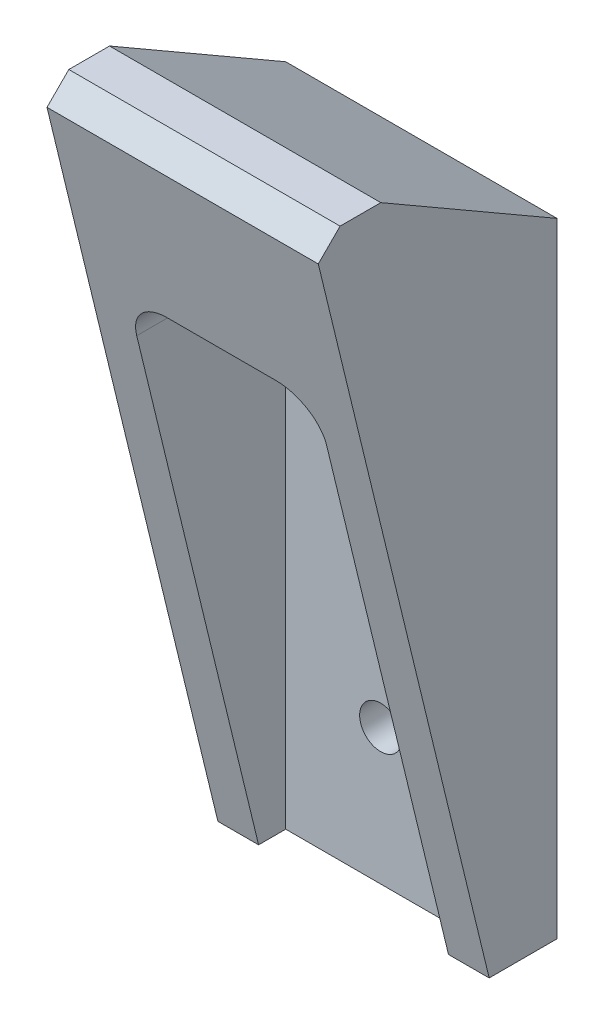
SolidWorks part; units mm, degrees
ref_plane "Front Plane" through (0, 0, 0) normal (0, 0, 1) x (1, 0, 0)
ref_plane "Top Plane" through (0, 0, 0) normal (0, 1, 0) x (1, 0, 0)
ref_plane "Right Plane" through (0, 0, 0) normal (1, 0, 0) x (0, 0, -1)
sketch "Sketch1" plane through (0, 0, 0) normal (1, 0, 0) x (0, 0, -1)
  line L0 (0, 0) -> (-5, 0)
  line L1 (0, 0) -> (0, 46)
  line L2 (0, 46) -> (-12.9904, 53.5)
  line L3 (-12.9904, 53.5) -> (-17.9904, 53.5)
  line L4 (-17.9904, 53.5) -> (-5, 0)
  dimension "D1" = 5
  dimension "D2" = 46
  dimension "D3" = 120
  dimension "D4" = 15
  dimension "D5" = 5
extrude "Boss-Extrude1" add sketch "Sketch1" along normal blind 20
ref_plane "Plane1" through (0, 0, 0) normal (0, -1, 0) x (-1, 0, 0)
ref_point "Point1"
ref_plane "Plane2" through (0, 0, 17.9904) normal (0, 0, 1) x (1, 0, 0)
sketch "Sketch4" plane through (0, 0, 17.9904) normal (0, 0, 1) x (1, 0, 0)
  line L0 (10, 0) -> (10, 53.5) construction
  line L1 (0, 0) -> (3, 0)
  line L2 (20, 0) -> (17, 0)
  line L3 (3, 0) -> (3, 40)
  line L4 (0, 53.5) -> (0, 0)
  line L5 (0, 0) -> (20, 0)
  line L6 (20, 0) -> (20, 53.5)
  line L7 (20, 53.5) -> (0, 53.5)
  line L8 (0, 53.5) -> (0, 0)
  line L9 (0, 0) -> (20, 0)
  line L10 (20, 0) -> (20, 53.5)
  line L11 (20, 53.5) -> (0, 53.5)
  line L12 (3, 40) -> (17, 40)
  line L13 (17, 40) -> (17, 0)
  dimension "D2" = 3
  dimension "D3" = 3
  dimension "D4" = 40
  dimension "D1" = 0
extrude "Cut-Extrude1" cut sketch "Sketch4" against normal offset from surface (14.9904 mm away) 3 contours L0 L9 L13 L12 | L9 L0 L12 L3 region at (6.5, 20, 17.9904) region at (13.5, 20, 17.9904) up to face at (10, 23, 0)
sketch "Sketch5" plane through (0, 0, 3) normal (0, 0, 1) x (1, 0, 0)
  line L0 (10, 0) -> (10, 53.1114) construction
  line L1 (17, 0) -> (3, 0) construction
  line L2 (17, 40) -> (3, 40) construction
  point P4 (10, 10)
  point P5 (10, 30)
  dimension "D1" = 10
  dimension "D2" = 10
fillet "Fillet1" radius 3 2 edges at (3, 40, 8.8562) (17, 40, 8.8562)
chamfer "Chamfer1" distance 2 angle 45 1 edges at (10, 53.5, 17.9904) first distance on face at (10, 53.5, 15.4904)
hole_wizard "M3 Clearance" positions "3DSketch1" profile "Sketch7" hole size "M" standard "ANSI Inch" end condition through all
sketch3d "3DSketch1"
  point P0 (10, 30, 3)
  point P3 (10, 10, 3)
sketch "Sketch7" plane through (10, 30, 3) normal (1, 0, 0) x (0, -1, 0)
  line L0 (0, 0) -> (0, 3)
  line L1 (0, 3) -> (1.55, 3)
  line L2 (1.55, 3) -> (1.55, 0)
  line L5 (1.55, 0) -> (0, 0)
  line L11 (0, -6.35) -> (0, 107.95) construction
  dimension "Thru Hole Dia." = 3.1
  dimension "Thru Hole Depth" = 3
